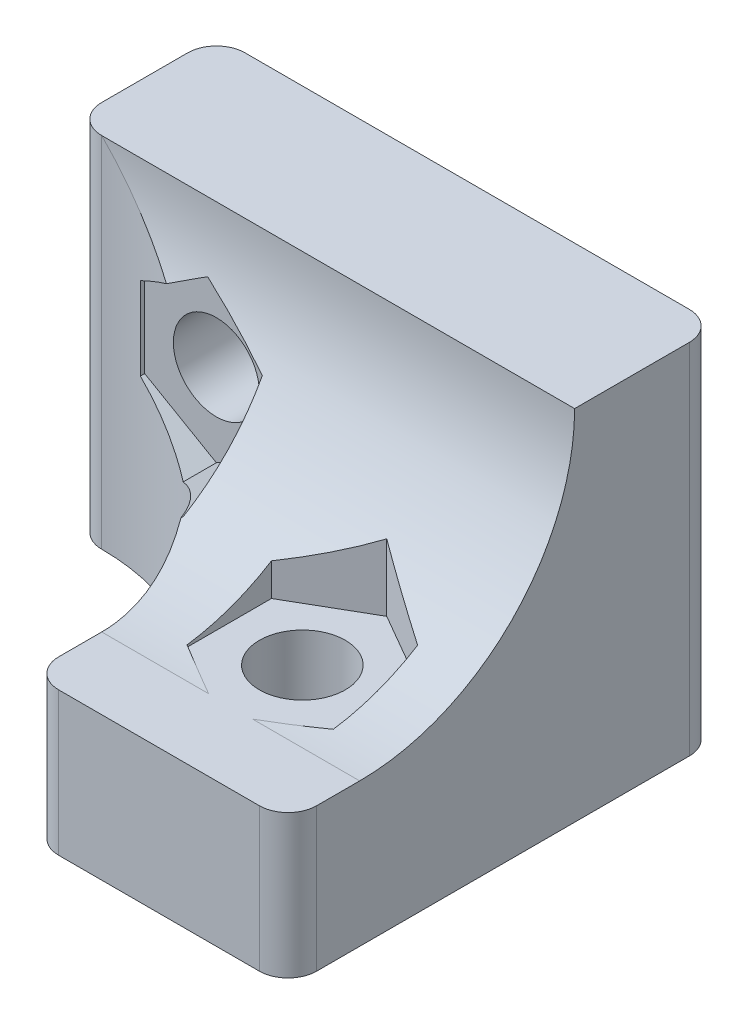
SolidWorks part; units mm, degrees
ref_plane "Front Plane" through (0, 0, 0) normal (0, 0, 1) x (1, 0, 0)
ref_plane "Top Plane" through (0, 0, 0) normal (0, 1, 0) x (1, 0, 0)
ref_plane "Right Plane" through (0, 0, 0) normal (1, 0, 0) x (0, 0, -1)
sketch "Sketch1" plane through (0, 0, 0) normal (0, 0, 1) x (1, 0, 0)
  line L1 (-17.5, 12.5) -> (17.5, 12.5)
  line L2 (-17.5, 12.5) -> (-17.5, -12.5)
  line L3 (-17.5, -12.5) -> (17.5, -12.5)
  line L4 (17.5, 12.5) -> (17.5, -12.5)
  line L5 (-17.5, 12.5) -> (17.5, -12.5) construction
  line L6 (-17.5, -12.5) -> (17.5, 12.5) construction
  point P0 (0, 0)
  dimension "D1" = 25
  dimension "D2" = 35
extrude "Boss-Extrude1" add sketch "Sketch1" along normal blind 10
sketch "Sketch2" plane through (0, 0, 10) normal (0, 0, 1) x (1, 0, 0)
  line L0 (-17.5, -12.5) -> (-7.5, -12.5) construction
  line L1 (-17.5, -12.5) -> (17.5, -12.5) construction
  line L2 (-7.5, -12.5) -> (-7.5, 2.5) construction
  circle A0 centre (-7.5, 2.5) radius 3
  dimension "D3" = 6
  dimension "D1" = 10
  dimension "D2" = 15
extrude "Cut-Extrude1" cut sketch "Sketch2" against normal through all
sketch "Sketch3" plane through (0, 0, 10) normal (0, 0, 1) x (1, 0, 0)
  line L1 (17.5, -12.5) -> (-0.5, -12.5)
  line L2 (17.5, -12.5) -> (17.5, -2.5)
  line L3 (17.5, -2.5) -> (-0.5, -2.5)
  line L4 (-0.5, -12.5) -> (-0.5, -2.5)
  dimension "D1" = 18
  dimension "D2" = 10
extrude "Boss-Extrude2" add sketch "Sketch3" along normal blind 20
sketch "Sketch4" plane through (0, -2.5, 0) normal (0, 1, 0) x (1, 0, 0)
  line L0 (17.5, -10) -> (8.5, -10) construction
  line L1 (17.5, -10) -> (-0.5, -10) construction
  line L2 (8.5, -10) -> (8.5, -20) construction
  circle A0 centre (8.5, -20) radius 3
  dimension "D3" = 6
  dimension "D1" = 9
  dimension "D2" = 10
extrude "Cut-Extrude2" cut sketch "Sketch4" against normal through all contours A0
fillet "Fillet2" radius 15 2 edges at (-0.5, -7.5, 10) (8.5, -2.5, 10)
fillet "Fillet3" radius 2 5 edges at (17.5, 0, 0) (-17.5, 0, 0) (-17.5, 0, 10) (-0.5, -7.5, 30) (17.5, -7.5, 30)
sketch "Sketch5" plane through (0, 0, 0) normal (0, 0, -1) x (-1, 0, 0)
  line L1 (7.5, -3.2735) -> (12.5, -0.3868)
  line L2 (12.5, -0.3868) -> (12.5, 5.3868)
  line L3 (12.5, 5.3868) -> (7.5, 8.2735)
  line L4 (7.5, 8.2735) -> (2.5, 5.3868)
  line L5 (2.5, 5.3868) -> (2.5, -0.3868)
  line L6 (2.5, -0.3868) -> (7.5, -3.2735)
  line L7 (7.5, -3.389) -> (12.6, -0.4445)
  line L8 (12.6, -0.4445) -> (12.6, 5.4445)
  line L9 (12.6, 5.4445) -> (7.5, 8.389)
  line L10 (7.5, 8.389) -> (2.4, 5.4445)
  line L11 (2.4, 5.4445) -> (2.4, -0.4445)
  line L12 (2.4, -0.4445) -> (7.5, -3.389)
  circle A0 centre (7.5, 2.5) radius 5 construction
  circle A1 centre (7.5, 2.5) radius 5.1 construction
  circle M1 centre (7.5, 2.5) radius 3
extrude "Cut-Extrude3" cut sketch "Sketch5" against normal through all from offset 10 contours L5 L6 L1 L2 L3 L4 M1 | L1 L2 L3 L4 L5 L6 region at (-5.0764, -1.6978, 0) offset against normal yes
sketch "Sketch6" plane through (0, -12.5, 0) normal (0, -1, 0) x (1, 0, 0)
  line L1 (8.5, 14.111) -> (13.6, 17.0555)
  line L2 (13.6, 17.0555) -> (13.6, 22.9445)
  line L3 (13.6, 22.9445) -> (8.5, 25.889)
  line L4 (8.5, 25.889) -> (3.4, 22.9445)
  line L5 (3.4, 22.9445) -> (3.4, 17.0555)
  line L6 (3.4, 17.0555) -> (8.5, 14.111)
  circle A0 centre (8.5, 20) radius 5.1 construction
extrude "Cut-Extrude4" cut sketch "Sketch6" against normal through all from offset 10 offset against normal yes
